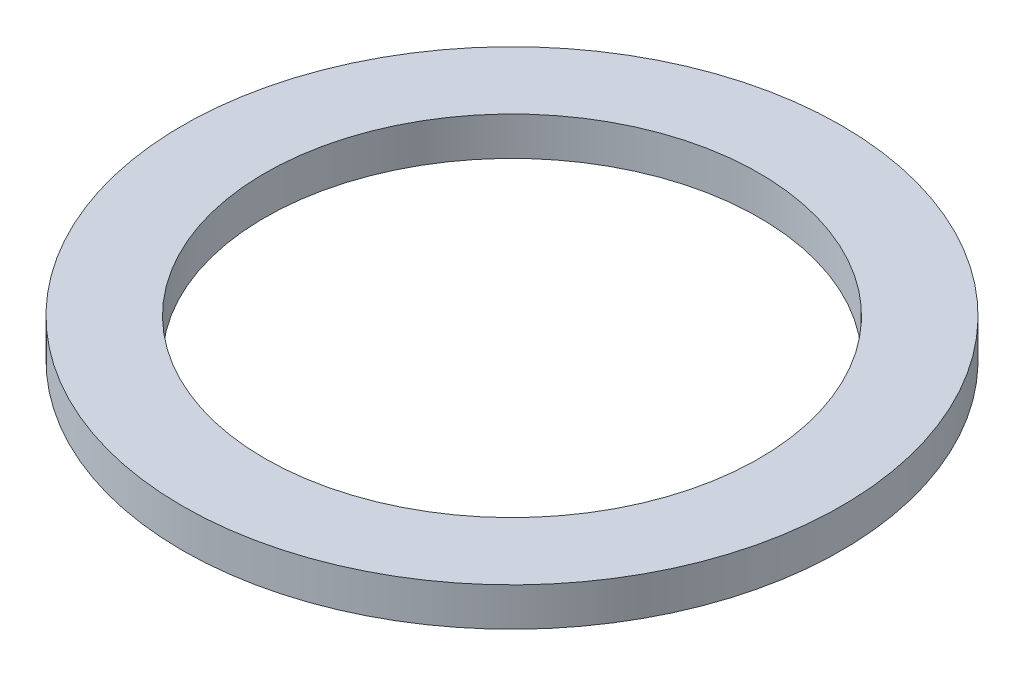
SolidWorks part; units mm, degrees
ref_plane "Front Plane" through (0, 0, 0) normal (0, 0, 1) x (1, 0, 0)
ref_plane "Top Plane" through (0, 0, 0) normal (0, 1, 0) x (1, 0, 0)
ref_plane "Right Plane" through (0, 0, 0) normal (1, 0, 0) x (0, 0, -1)
sketch "Sketch1" plane through (0, 0, 0) normal (0, 1, 0) x (1, 0, 0)
  circle A0 centre (0, 0) radius 60
  dimension "FLANGE_OD" = 120
extrude "Boss-Extrude1" add sketch "Sketch1" along normal blind 7
sketch "Sketch2" plane through (0, 0, 0) normal (0, 1, 0) x (1, 0, 0)
  circle A0 centre (0, 0) radius 45
  dimension "BORE_D" = 90
extrude "Cut-Extrude1" cut sketch "Sketch2" along normal through all
sketch "Sketch3" plane through (0, 7, 0) normal (0, 1, 0) x (1, 0, 0)
  circle A0 centre (0, 0) radius 26.7164 construction
  circle A1 centre (-26.7164, 0) radius 2.5442
  dimension "BOLT_D" = 5.0884
  dimension "BOLT_PCD" = 53.4329
extrude "Cut-Extrude2" cut sketch "Sketch3" against normal blind 4.592 rebuild error yes
pattern_circular "CirPattern1" count 5 over 360 rebuild error yes
